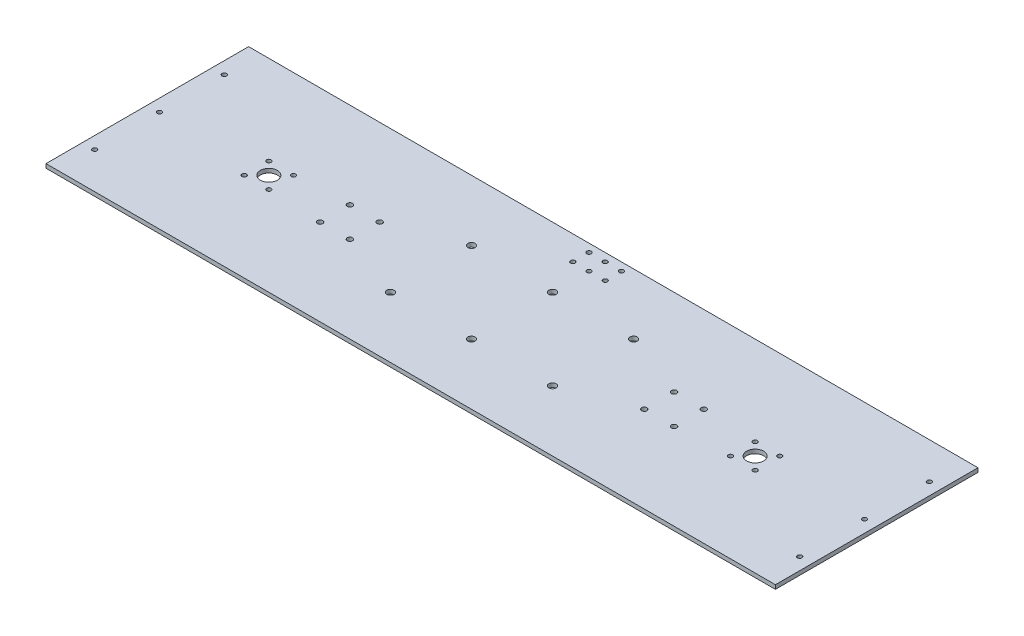
SolidWorks part; units mm, degrees
ref_plane "前视基准面" through (0, 0, 0) normal (0, 0, 1) x (1, 0, 0)
ref_plane "上视基准面" through (0, 0, 0) normal (0, 1, 0) x (1, 0, 0)
ref_plane "右视基准面" through (0, 0, 0) normal (1, 0, 0) x (0, 0, -1)
sketch "草图1" plane through (0, 0, 0) normal (0, 1, 0) x (1, 0, 0)
  line L0 (-900, 125) -> (0, 125) construction
  line L1 (0, 0) -> (-900, 0)
  line L2 (0, 0) -> (0, 250)
  line L3 (0, 250) -> (-900, 250)
  line L4 (-900, 0) -> (-900, 250)
  line L5 (-450, 250) -> (-450, 0) construction
  line L6 (-750, 125) -> (-810.1785, 185.1785) construction
  line L7 (-668.3848, 143.3848) -> (-650, 125) construction
  line L8 (-750, 172.7223) -> (-750, 125) construction
  line L9 (-650, 177.641) -> (-650, 125) construction
  circle A0 centre (-550, 175) radius 4.5
  circle A1 centre (-450, 175) radius 4.5
  circle A2 centre (-350, 175) radius 4.5
  circle A3 centre (-350, 75) radius 4.5
  circle A4 centre (-450, 75) radius 4.5
  circle A5 centre (-550, 75) radius 4.5
  circle A6 centre (-750, 125) radius 10.5
  circle A7 centre (-150, 125) radius 10.5
  circle A8 centre (-765.2028, 140.2028) radius 2.75
  circle A9 centre (-668.3848, 143.3848) radius 3.3
  circle A10 centre (-231.6152, 143.3848) radius 3.3
  circle A11 centre (-134.7972, 140.2028) radius 2.75
  circle A12 centre (-734.7972, 140.2028) radius 2.75
  circle A13 centre (-734.7972, 109.7972) radius 2.75
  circle A14 centre (-765.2028, 109.7972) radius 2.75
  circle A15 centre (-631.6152, 143.3848) radius 3.3
  circle A16 centre (-631.6152, 106.6152) radius 3.3
  circle A17 centre (-668.3848, 106.6152) radius 3.3
  circle A18 centre (-268.3848, 143.3848) radius 3.3
  circle A19 centre (-268.3848, 106.6152) radius 3.3
  circle A20 centre (-231.6152, 106.6152) radius 3.3
  circle A21 centre (-165.2028, 109.7972) radius 2.75
  circle A22 centre (-134.7972, 109.7972) radius 2.75
  circle A23 centre (-165.2028, 140.2028) radius 2.75
  point P7 (-750, 125)
  point P8 (-650, 125)
  point P9 (-450, 125)
  point P12 (-250, 125)
  point P13 (-150, 125)
  point P14 (-550, 175)
  point P15 (-450, 175)
  point P17 (-450, 75)
  point P18 (-550, 75)
  point P19 (-350, 175)
  point P20 (-350, 75)
  point P36 (-765.2028, 140.2028)
  point P43 (-668.3848, 143.3848)
  dimension "D7" = 9
  dimension "D8" = 21
  dimension "D9" = 21
  dimension "D10" = 5.5
  dimension "D14" = 6.6
  dimension "D15" = 26
  dimension "D1" = 900
  dimension "D2" = 250
  dimension "D3" = 150
  dimension "D4" = 100
  dimension "D5" = 100
  dimension "D6" = 50
  dimension "D11" = 45
  dimension "D12" = 21.5
  dimension "D13" = 45
extrude "凸台-拉伸1" add sketch "草图1" along normal blind 5
sketch "草图2" plane through (0, 5, 0) normal (0, 1, 0) x (1, 0, 0)
  line L0 (-450, 250) -> (-450, 0) construction
  line L1 (0, 250) -> (-900, 250) construction
  line L2 (-900, 0) -> (0, 0) construction
  line L3 (-885, 250) -> (-885, 0) construction
  line L4 (-430, 220) -> (-470, 220) construction
  line L5 (-430, 220) -> (-430, 240) construction
  line L6 (-430, 240) -> (-470, 240) construction
  line L7 (-470, 220) -> (-470, 240) construction
  line L8 (-430, 220) -> (-470, 240) construction
  line L9 (-430, 240) -> (-470, 220) construction
  line L10 (-900, 250) -> (-900, 0) construction
  line L11 (-900, 125) -> (-590.7904, 125) construction
  circle A0 centre (-470, 240) radius 2.75
  circle A1 centre (-430, 240) radius 2.75
  circle A2 centre (-430, 220) radius 2.75
  circle A3 centre (-470, 220) radius 2.75
  circle A4 centre (-450, 220) radius 2.75
  circle A5 centre (-450, 240) radius 2.75
  circle A6 centre (-885, 205) radius 2.75
  circle A7 centre (-885, 125) radius 2.75
  circle A8 centre (-885, 45) radius 2.75
  circle A9 centre (-15, 205) radius 2.75
  circle A10 centre (-15, 125) radius 2.75
  circle A11 centre (-15, 45) radius 2.75
  point P6 (-450, 230)
  dimension "D4" = 5.5
  dimension "D6" = 5.5
  dimension "D7" = 80
  dimension "D1" = 40
  dimension "D2" = 20
  dimension "D3" = 10
  dimension "D5" = 15
extrude "切除-拉伸1" cut sketch "草图2" against normal through all
